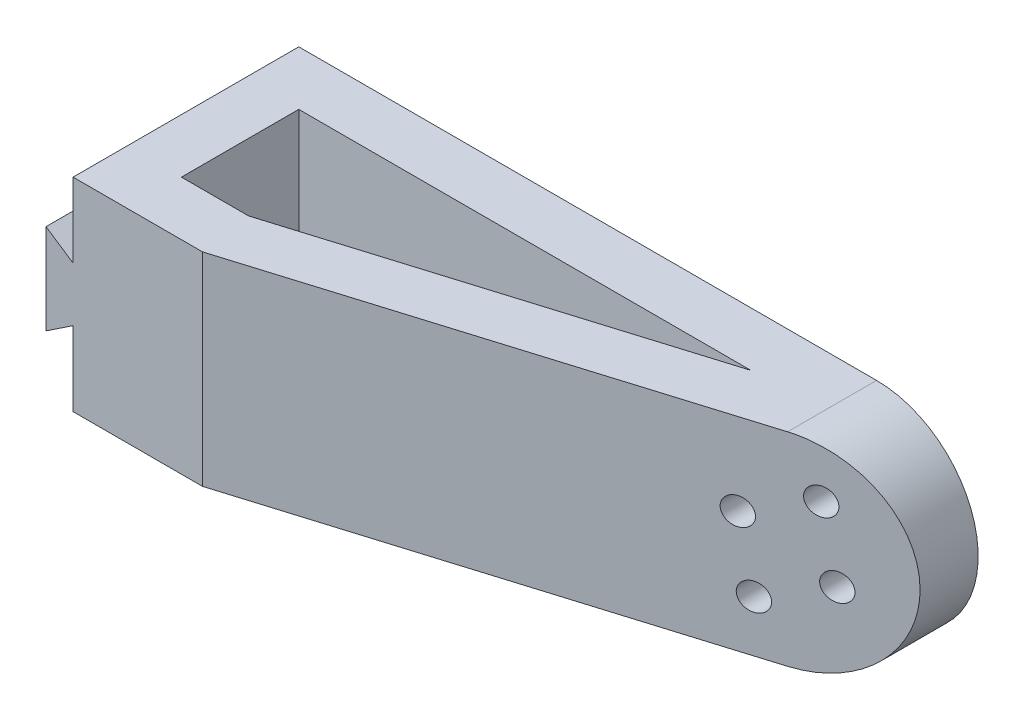
SolidWorks part; units mm, degrees
ref_plane "Front Plane" through (0, 0, 0) normal (0, 0, 1) x (1, 0, 0)
ref_plane "Top Plane" through (0, 0, 0) normal (0, 1, 0) x (1, 0, 0)
ref_plane "Right Plane" through (0, 0, 0) normal (1, 0, 0) x (0, 0, -1)
sketch "Sketch1" plane through (0, 0, 0) normal (0, 0, 1) x (1, 0, 0)
  line L0 (0, -22.5) -> (0, 22.5)
  line L1 (55, 0) -> (-55, 0) construction
  circle A0 centre (128, 0) radius 22.5
  circle A1 centre (133.7176, 11.1157) radius 2
  circle A2 centre (136.4479, -4.3454) radius 2
  circle A3 centre (122.2824, -11.1157) radius 2
  circle A4 centre (119.5521, 4.3454) radius 2
  spline S0 degree 1 poles (0, 22.5) (128, 22.5) knots 0 0 1 1
  spline S1 degree 1 poles (0, -22.5) (128, -22.5) knots 0 0 1 1
  point P4 (0, 0)
  dimension "D1" = 45
  dimension "D4" = 4
  dimension "D5" = 4
  dimension "D6" = 4
  dimension "D7" = 4
  dimension "D2" = 128
  dimension "D3" = 45
extrude "Boss-Extrude1" add sketch "Sketch1" along normal mid plane 50 contours L0 S1 A0 S0 | A0 region at (55.2786, 0, 0) region at (128, 0, 0)
sketch "Sketch2" plane through (0, 0, 0) normal (0, 1, 0) x (1, 0, 0)
  line L0 (0, -25) -> (28.6696, -25)
  line L1 (0, -25) -> (128, -25) construction
  line L2 (28.6696, -25) -> (150.5, 12.1415)
  line L3 (150.5, -25) -> (150.5, 25) construction
  line L4 (150.5, 12.1415) -> (150.5, 25)
  line L5 (150.5, 25) -> (0, 25)
  line L6 (0, 25) -> (0, -25)
extrude "Cut-Extrude2" cut sketch "Sketch2" against normal mid plane 50 flip side to cut contours L5 L6 L0 L2 L4 region at (60.3575, 0, -5.4254)
sketch "Sketch5" plane through (0, 0, 0) normal (0, 0, 1) x (1, 0, 0)
  line L0 (0, -6) -> (0, 6)
  line L1 (0, -22.5) -> (0, 22.5) construction
  line L9 (0, 6) -> (-6, 10)
  line L10 (-6, 10) -> (-6, -10)
  line L11 (-6, -10) -> (0, -6)
  point P5 (0, 0)
  dimension "D1" = 12
  dimension "D2" = 20
  dimension "D3" = 6
extrude "Boss-Extrude2" add sketch "Sketch5" along normal up to surface (25 mm away) from surface up to face at (14.3348, 0, 25) starting at face at (69.625, 0, -25)
sketch "Sketch3" plane through (0, 0, 0) normal (0, 1, 0) x (1, 0, 0)
  line L91 (12, 13) -> (12, -13)
  line L92 (12, -13) -> (26.881, -13)
  line L93 (26.881, -13) -> (112.1656, 13)
  line L95 (112.1656, 13) -> (12, 13)
  line L96 (12, 13) -> (12, -13)
  line L97 (12, -13) -> (26.881, -13)
  line L98 (26.881, -13) -> (112.1656, 13)
  line L100 (112.1656, 13) -> (12, 13)
  dimension "D1" = 12
extrude "Cut-Extrude3" cut sketch "Sketch3" against normal mid plane 50
ref_plane "Plane2" through (0, 0, 0) normal (0, 0, -1) x (-1, 0, 0)
hole_wizard "CBORE for M3 Hex Head Machine Screw3" positions "Sketch16" profile "Sketch18" counterbore size "M3" standard "ANSI Metric"
sketch "Sketch16" plane through (0, 0, 0) normal (0, 0, -1) x (-1, 0, 0)
  point P0 (-133.7176, 11.1157)
  point P3 (-119.5521, 4.3454)
  point P6 (-122.2824, -11.1157)
  point P9 (-136.4479, -4.3454)
sketch "Sketch18" plane through (133.7176, 11.1157, 0) normal (1, 0, 0) x (0, -1, 0)
  line L0 (0, 0) -> (0, 25.9013)
  line L1 (0, 25.9013) -> (1.5, 25)
  line L2 (1.5, 25) -> (1.5, 14)
  line L3 (1.5, 14) -> (3, 14)
  line L4 (3, 14) -> (3, 0)
  line L5 (3, 0) -> (0, 0)
  line L10 (0, 25.9013) -> (-1.5, 25) construction
  line L11 (0, -6.35) -> (0, 107.95) construction
  dimension "Hole Dia." = 3
  dimension "Hole Depth" = 25
  dimension "C'Bore Dia." = 6
  dimension "C'Bore Depth" = 14
  dimension "Drill Angle" = 118
